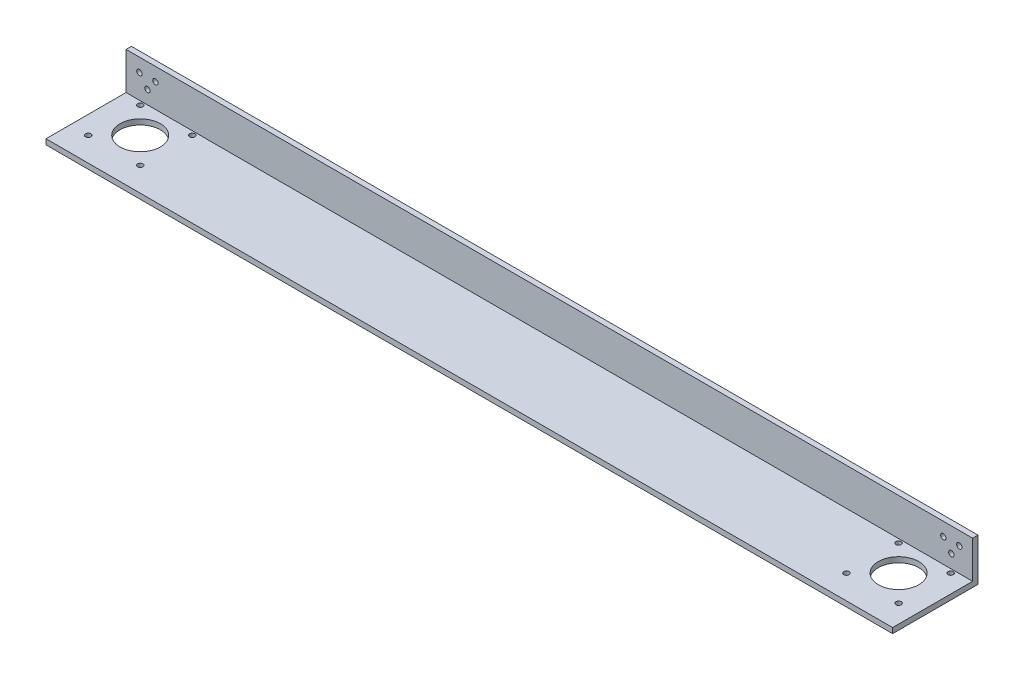
SolidWorks part; units mm, degrees
ref_plane "Front Plane" through (0, 0, 0) normal (0, 0, 1) x (1, 0, 0)
ref_plane "Top Plane" through (0, 0, 0) normal (0, 1, 0) x (1, 0, 0)
ref_plane "Right Plane" through (0, 0, 0) normal (1, 0, 0) x (0, 0, -1)
sketch "Sketch1" plane through (0, 0, 0) normal (1, 0, 0) x (0, 0, -1)
  line L0 (0, 0) -> (-50.8, 0)
  line L1 (-50.8, 0) -> (-50.8, 3.175)
  line L2 (-50.8, 3.175) -> (-3.175, 3.175)
  line L3 (-3.175, 3.175) -> (-3.175, 25.4)
  line L4 (-3.175, 25.4) -> (0, 25.4)
  line L5 (0, 25.4) -> (0, 0)
  dimension "LHeight" = 25.4
  dimension "LWidth" = 50.8
  dimension "LMaterialThickness" = 3.175
  dimension "D1" = 47.625
  dimension "D2" = 22.225
  dimension "D3" = 3.175
extrude "Boss-Extrude1" add sketch "Sketch1" along normal blind 503.65
sketch "TopHoles-Sketch2" plane through (0, 3.175, 0) normal (0, 1, 0) x (1, 0, 0)
  line L2 (0, -3.175) -> (0, -50.8) construction
  line L3 (503.65, -3.175) -> (503.65, -50.8) construction
  circle A0 centre (26.25, -21) radius 12
  circle A1 centre (477.4, -21) radius 12
  circle A2 centre (10.75, -5.5) radius 1.5875
  circle A3 centre (41.75, -5.5) radius 1.5875
  circle A4 centre (461.9, -5.5) radius 1.5875
  circle A5 centre (492.9, -5.5) radius 1.5875
  circle A6 centre (10.75, -36.5) radius 1.5875
  circle A7 centre (41.75, -36.5) radius 1.5875
  circle A8 centre (461.9, -36.5) radius 1.5875
  circle A9 centre (492.9, -36.5) radius 1.5875
  dimension "D9" = 3.175
  dimension "D10" = 24
  dimension "D2" = 5.5
  dimension "D3" = 31
  dimension "D4" = 15.5
  dimension "D5" = 15.5
  dimension "D6" = 31
  dimension "D7" = 15.5
  dimension "D13" = 26.25
  dimension "D8" = 31
  dimension "D11" = 26.25
extrude "TopHoles-Cut-Extrude1" cut sketch "TopHoles-Sketch2" against normal through all
sketch "BackSideHoles-Sketch3" plane through (0, 0, 0) normal (0, 0, -1) x (-1, 0, 0)
  line L1 (-503.65, 25.4) -> (0, 25.4) construction
  line L2 (0, 0) -> (0, 25.4) construction
  line L3 (-503.65, 0) -> (-503.65, 25.4) construction
  circle A0 centre (-495.7125, 17.4625) radius 1.5875
  circle A1 centre (-486.1875, 17.4625) radius 1.5875
  circle A3 centre (-490.95, 11.1125) radius 1.5875
  circle A4 centre (-12.7, 11.1125) radius 1.5875
  circle A6 centre (-17.4625, 17.4625) radius 1.5875
  circle A7 centre (-7.9375, 17.4625) radius 1.5875
  dimension "D7" = 3.175
  dimension "D4" = 11.1125
  dimension "D3" = 7.9375
  dimension "D1" = 7.9375
  dimension "D2" = 17.4625
  dimension "D6" = 17.4625
  dimension "D5" = 7.9375
  dimension "D8" = 12.7
  dimension "D9" = 12.7
extrude "BackSideHoles-Cut-Extrude2" cut sketch "BackSideHoles-Sketch3" against normal through all
equation "\"MidBackRailWidth\"= 2.00in"
equation "\"MidBackRailHeight\"= 1.00in"
equation "\"RailThickness\"= .125in'Spec"
equation "\"SideRailHoleY1FromEdge\"= \"HoleOffsetFromEdge\""
equation "\"SideRailHoleX1FromSide\"= \"HoleOffsetFromSide\""
equation "\"StepperHoleDiameter\"= 24mm"
equation "\"StepperMountingHoleDiameter\"= 3.175mm"
equation "\"StepperMountingHoleDistance\"= 31mm'Spec"
equation "\"VSWidth\"= 1.25in'Spec"
equation "\"StepperMountingHoleOffsetFromLeftRightEdge\"= \"StepperMountingHoleOffsetFromItsSide\""
equation "\"HoleOffsetFromEdge\"= \"RailThickness\" * 2.5"
equation "\"HoleOffsetFromSide\"= \"RailThickness\" * 3.5"
equation "\"StepperMountingHoleOffsetFromItsSide\"= 5.5mm'Spec"
equation "\"SideRailHoleX2FromSide\"= \"VSWidth\" - \"HoleOffsetFromEdge\" - \"RailThickness\"'Equals 20.6375"
equation "\"FasteningHoleDiameter\"= .125in"
equation "\"SideRailHoleY2FromSide\"= \"HoleOffsetFromSide\""
equation "\"FrontBackRailLength\"= 510mm"
equation "\"LHeight@Sketch1\"=\"MidBackRailHeight\""
equation "\"LWidth@Sketch1\"=\"MidBackRailWidth\""
equation "\"D2@TopHoles-Sketch2\" = \"StepperMountingHoleOffsetFromLeftRightEdge\""
equation "\"D3@TopHoles-Sketch2\" = \"StepperMountingHoleDistance\""
equation "\"D4@TopHoles-Sketch2\" = \"StepperMountingHoleDistance\" / 2"
equation "\"D5@TopHoles-Sketch2\" = \"StepperMountingHoleDistance\" / 2"
equation "\"D6@TopHoles-Sketch2\" = \"StepperMountingHoleDistance\""
equation "\"D7@TopHoles-Sketch2\" = \"StepperMountingHoleDistance\" / 2"
equation "\"D9@TopHoles-Sketch2\" = \"StepperMountingHoleDiameter\""
equation "\"D10@TopHoles-Sketch2\" = \"StepperHoleDiameter\""
equation "\"D4@BackSideHoles-Sketch3\" = \"SideRailHoleY2FromSide\""
equation "\"D7@BackSideHoles-Sketch3\" = \"FasteningHoleDiameter\""
equation "\"D1@Boss-Extrude1\"= \"MidBackRailLength\""
equation "\"D3@BackSideHoles-Sketch3\"=\"SideRailHoleY1FromEdge\""
equation "\"D1@BackSideHoles-Sketch3\"=\"SideRailHoleX1FromSide\" - \"RailThickness\""
equation "\"D2@BackSideHoles-Sketch3\"=\"SideRailHoleX2FromSide\" - \"RailThickness\""
equation "\"D6@BackSideHoles-Sketch3\"=\"SideRailHoleX2FromSide\" - \"RailThickness\""
equation "\"D5@BackSideHoles-Sketch3\"=\"SideRailHoleX1FromSide\" - \"RailThickness\""
equation "\"StepperHoleToAlignHorizontallyWithGantryBlock\"= \"LinearGBWithRailDepth\" + \"GABDistanceFromBackToFirstPulley\"'Equals 26.25"
equation "\"D13@TopHoles-Sketch2\"=\"StepperHoleToAlignHorizontallyWithGantryBlock\" "
equation "\"D8@TopHoles-Sketch2\"=\"StepperMountingHoleDistance\""
equation "\"D11@TopHoles-Sketch2\"=\"StepperHoleToAlignHorizontallyWithGantryBlock\" "
equation "\"LinearGBWithRailDepth\"= 12.75mm'Spec"
equation "\"GABDistanceFromBackToFirstPulley\"= 13.5mm"
equation "\"MidBackRailLength\"= \"FrontBackRailLength\" - \"RailThickness\" * 2'MidBackRail buts up against MidSideRail"
equation "\"VSMidSideRailHoleXFromSideToCenter\"= \"RailThickness\" * 6"
equation "\"D8@BackSideHoles-Sketch3\"=\"VSMidSideRailHoleXFromSideToCenter\"- \"RailThickness\" - \"RailThickness\""
equation "\"D9@BackSideHoles-Sketch3\"=\"VSMidSideRailHoleXFromSideToCenter\" - \"RailThickness\" - \"RailThickness\""
